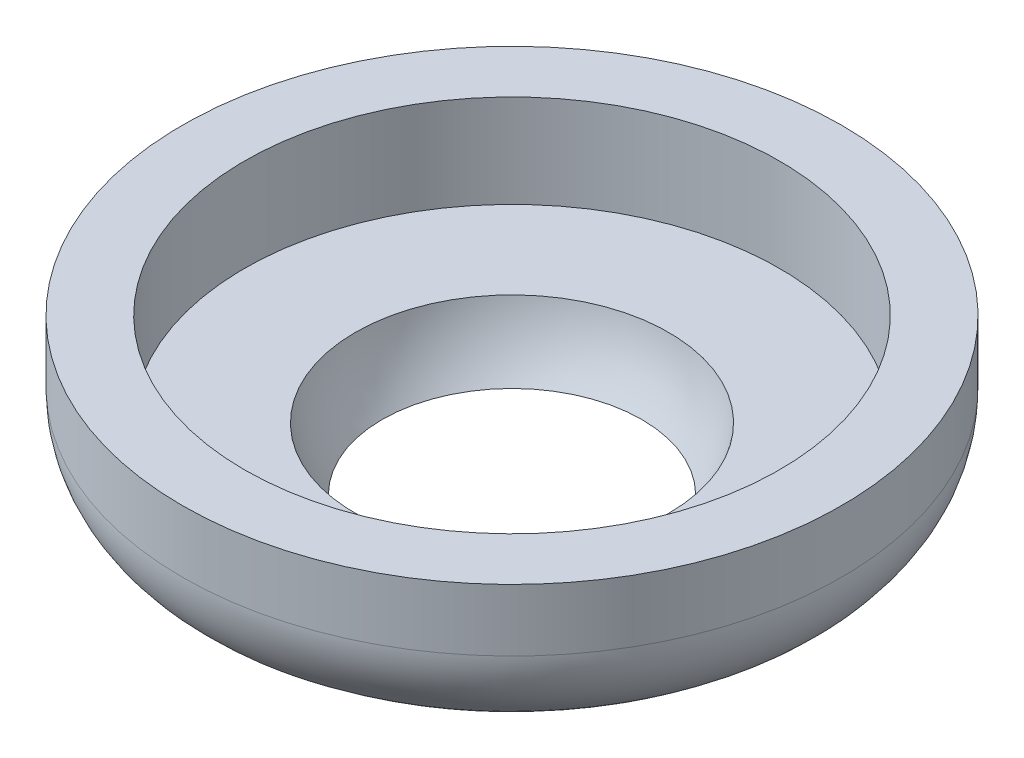
SolidWorks part; units mm, degrees
ref_plane "Alzado" through (0, 0, 0) normal (0, 0, 1) x (1, 0, 0)
ref_plane "Planta" through (0, 0, 0) normal (0, 1, 0) x (1, 0, 0)
ref_plane "Vista lateral" through (0, 0, 0) normal (1, 0, 0) x (0, 0, -1)
sketch "Croquis1" plane through (0, 0, 0) normal (0, 1, 0) x (1, 0, 0)
  circle A0 centre (0, 0) radius 8.625
  circle A1 centre (0, 0) radius 10.625
  dimension "D1" = 17.25
  dimension "D2" = 2
extrude "Saliente-Extruir1" add sketch "Croquis1" along normal blind 5 contours A1 A0 region at (-10.3245, 0, 0)
extrude "Saliente-Extruir2" add sketch "Croquis1<3>" along normal blind 2 contours A0 region at (0, 0, 0)
sketch "Croquis1<3>" plane through (0, 0, 0) normal (0, 1, 0) x (1, 0, 0) same geometry as "Croquis1"
sketch "Croquis2" plane through (0, 0, 0) normal (0, 0, 1) x (1, 0, 0)
  line L0 (8.625, 2) -> (-8.625, 2) construction
  line L1 (8.625, 2) -> (-8.625, 2) construction
  line L2 (0, 8.15) -> (0, -2.15)
  arc A0 (0, 8.15) -> (0, -2.15) centre (0, 3) ccw
  dimension "D1" = 10.3
  dimension "D2" = 1
revolve "Cortar-Revolución1" cut sketch "Croquis2" angle 360 about L2
fillet "Redondeo1" radius 3 1 edges at (0, 0, 10.625)
